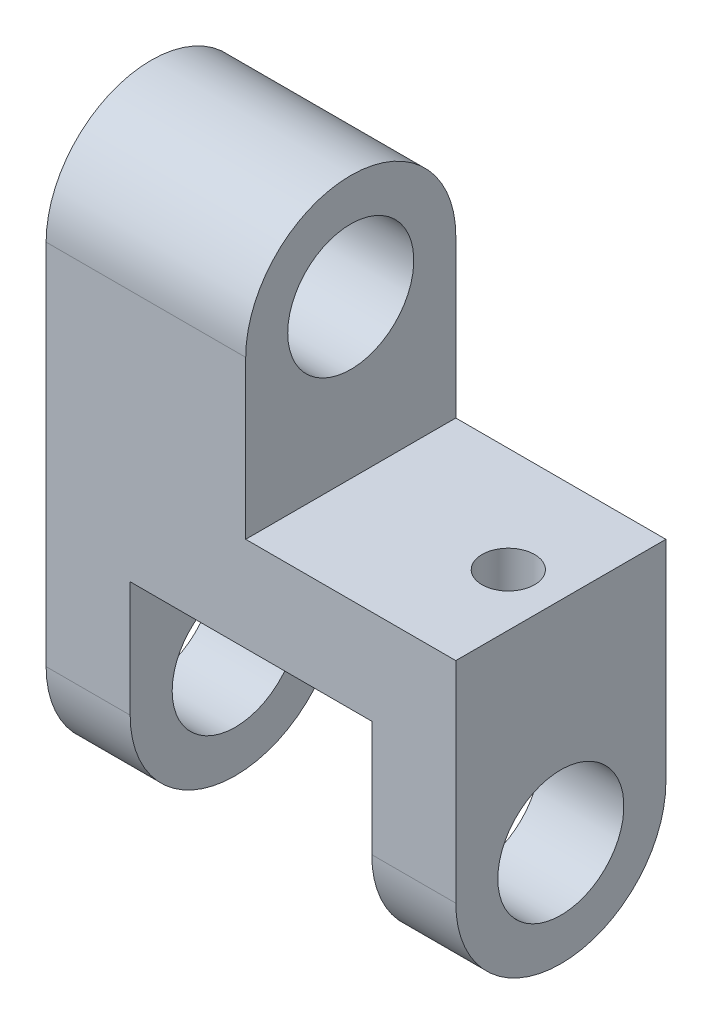
SolidWorks part; units mm, degrees
ref_plane "Спереди" through (0, 0, 0) normal (0, 0, 1) x (1, 0, 0)
ref_plane "Сверху" through (0, 0, 0) normal (0, 1, 0) x (1, 0, 0)
ref_plane "Справа" through (0, 0, 0) normal (1, 0, 0) x (0, 0, -1)
sketch "Эскиз1" plane through (0, 0, 0) normal (1, 0, 0) x (0, 0, -1)
  line L0 (0, 17.5) -> (0, -17.5) construction
  line L1 (10, 17.5) -> (10, -17.5)
  line L2 (-10, 17.5) -> (-10, -17.5)
  line L3 (-17.287, 0) -> (16.9614, 0) construction
  arc A0 (10, 17.5) -> (-10, 17.5) centre (0, 17.5) ccw
  arc A1 (-10, -17.5) -> (10, -17.5) centre (0, -17.5) ccw
  circle A2 centre (0, 17.5) radius 6
  circle A3 centre (0, -17.5) radius 6
  point P3 (0, 0)
  dimension "D1" = 55
  dimension "D3" = 12
  dimension "D2" = 20
extrude "Бобышка-Вытянуть1" add sketch "Эскиз1" along normal blind 39
sketch "Эскиз2" plane through (0, 0, 0) normal (0, 0, 1) x (1, 0, 0)
  line L0 (0, 17.5) -> (0, -17.5) construction
  line L1 (8, -6.5) -> (31, -6.5)
  line L2 (8, -6.5) -> (8, -40.5924)
  line L3 (8, -40.5924) -> (31, -40.5924)
  line L4 (31, -6.5) -> (31, -40.5924)
  line L5 (39, 17.5) -> (39, -17.5) construction
  line L6 (0, -27.5) -> (39, -27.5) construction
  dimension "D1" = 8
  dimension "D2" = 8
  dimension "D3" = 21
extrude "Вырез-Вытянуть1" cut sketch "Эскиз2" against normal through all and the other way through all
sketch "Эскиз3" plane through (0, 0, 0) normal (0, 0, 1) x (1, 0, 0)
  line L0 (0, 17.5) -> (0, -17.5) construction
  line L1 (19, 35.0973) -> (62.7132, 35.0973)
  line L2 (19, 35.0973) -> (19, 2.5)
  line L3 (19, 2.5) -> (62.7132, 2.5)
  line L4 (62.7132, 35.0973) -> (62.7132, 2.5)
  line L5 (31, -6.5) -> (8, -6.5) construction
  dimension "D1" = 19
  dimension "D2" = 9
extrude "Вырез-Вытянуть2" cut sketch "Эскиз3" against normal through all and the other way through all
sketch "Эскиз4" plane through (0, 2.5, 0) normal (0, 1, 0) x (1, 0, 0)
  line L0 (23.1159, 0) -> (39, 0) construction
  line L1 (39, -10) -> (39, 10) construction
  circle A0 centre (34, 0) radius 2.5
  dimension "D1" = 5
  dimension "D2" = 5
extrude "Вырез-Вытянуть3" cut sketch "Эскиз4" against normal blind 12
ref_plane "Средняя плоскость петли" through (19.5, 0, 0) normal (1, 0, 0) x (0, 0, -1)
